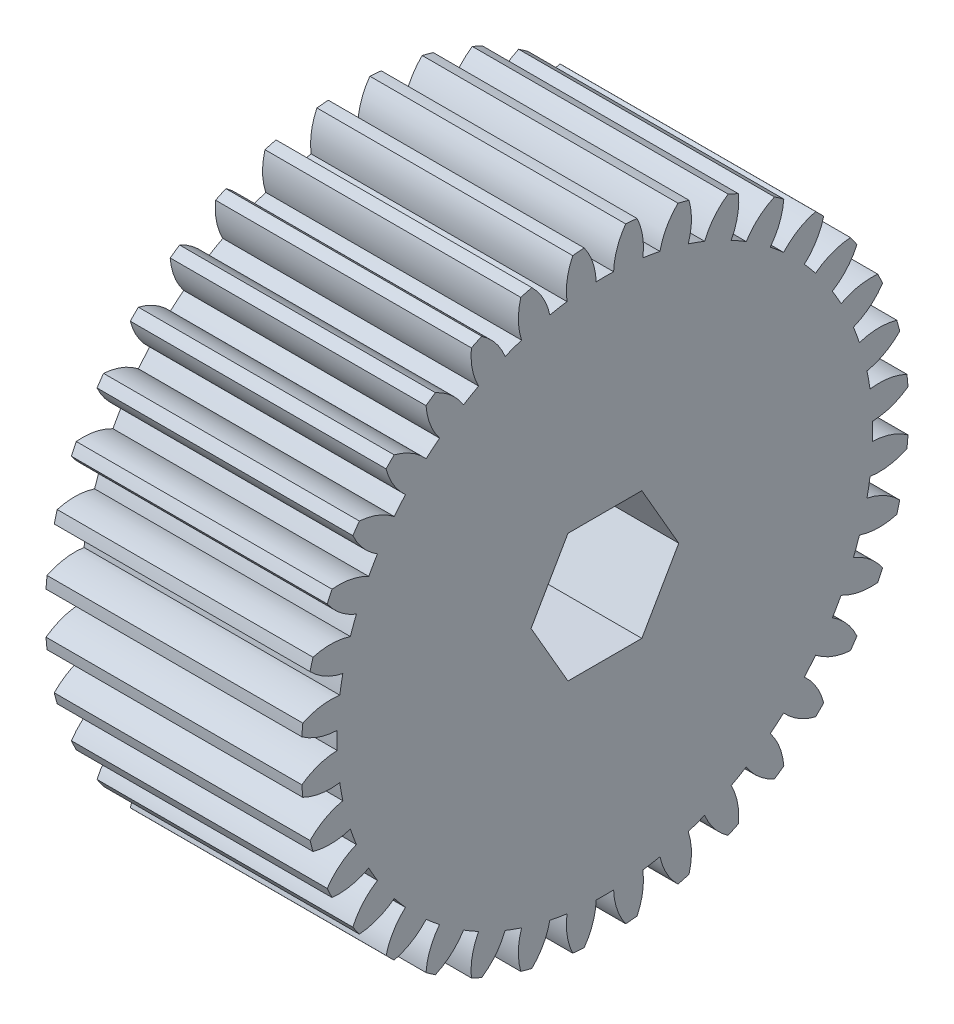
SolidWorks part; units mm, degrees
material "ABS"
ref_plane "Front Plane" through (0, 0, 0) normal (0, 0, 1) x (1, 0, 0)
ref_plane "Top Plane" through (0, 0, 0) normal (0, 1, 0) x (1, 0, 0)
ref_plane "Right Plane" through (0, 0, 0) normal (1, 0, 0) x (0, 0, -1)
sketch "Sketch1" plane through (0, 0, 0) normal (1, 0, 0) x (0, 0, -1)
  circle A0 centre (0, 0) radius 28.575
  circle A1 centre (0, 0) radius 30.1625
  circle A2 centre (0, 0) radius 26.5906
  dimension "D1" = 57.15
  dimension "D2" = 1.5875
  dimension "D3" = 3.5719
extrude "Boss-Extrude1" add sketch "Sketch1" along normal blind 25.4 contours A2 | A0 A2 | A1 A0 region at (0, 0, 27.7668) region at (0, 0, 29.3094) region at (0, 0, 0)
sketch "Sketch2" plane through (25.4, 0, 0) normal (1, 0, 0) x (0, 0, -1)
  line L0 (0, 0) -> (0, 30.1625) construction
  line L1 (0, 25.1233) -> (-1.2464, 28.5478) construction
  line L2 (-1.2464, 28.5478) -> (1.2464, 28.5478) construction
  line L3 (1.2464, 28.5478) -> (3.7298, 28.3305) construction
  line L4 (2.4881, 28.4392) -> (0, 0) construction
  line L5 (-0.8656, 26.5765) -> (0, 0) construction
  circle A0 centre (0, 0) radius 30.1625 construction
  arc A1 (-0.8656, 26.5765) -> (-2.6937, 30.8388) centre (-7.2322, 26.3692) ccw
  circle A2 centre (0, 0) radius 26.5906
  arc A3 (0.8656, 26.5765) -> (-0.8656, 26.5765) centre (0, 0) ccw
  circle A4 centre (0, 0) radius 30.1625
  circle A5 centre (0, 0) radius 30.1625 construction
  circle A6 centre (0, 0) radius 28.575
  circle A7 centre (0, 0) radius 28.575 construction
  arc A8 (2.6937, 30.8388) -> (-2.6937, 30.8388) centre (0, 0) ccw
  arc A9 (0.8656, 26.5765) -> (2.6937, 30.8388) centre (7.2322, 26.3692) cw
  point P22 (0, 11.9182)
  point P26 (-1.1112, 15.9084)
  dimension "D4" = 0.7937
  dimension "D5" = 5
  dimension "D6" = 20
extrude "Cut-Extrude1" cut sketch "Sketch2" against normal through all
pattern_circular "CirPattern1" count 36 over 360 about axis through (25.4, 0, 0) along (-1, 0, 0) of "Cut-Extrude1" reverse direction yes
sketch "Sketch3" plane through (25.4, 0, 0) normal (1, 0, 0) x (0, 0, -1)
  line L1 (3.6662, 6.35) -> (-3.6662, 6.35)
  line L2 (-3.6662, 6.35) -> (-7.3323, 0)
  line L3 (-7.3323, 0) -> (-3.6662, -6.35)
  line L4 (-3.6662, -6.35) -> (3.6662, -6.35)
  line L5 (3.6662, -6.35) -> (7.3323, 0)
  line L6 (7.3323, 0) -> (3.6662, 6.35)
  circle A0 centre (0, 0) radius 6.35 construction
  dimension "D1" = 12.7
extrude "Cut-Extrude2" cut sketch "Sketch3" against normal through all
sketch "Sketch4" plane through (25.4, 0, 0) normal (1, 0, 0) x (0, 0, -1)
  circle A0 centre (0, 0) radius 28.575
  point P2 (0, 0)
  dimension "D1" = 57.15
equation "\"Module\"= 1 / 16in"
equation "\"Number of Teeth\"= 36"
equation "\"D1@Sketch1\"=\"Module\" * \"Number of Teeth\""
equation "\"D2@Sketch1\"=\"Module\""
equation "\"D3@Sketch1\"=2.25 * \"Module\""
equation "\"D5@Sketch2\"=180 / \"Number of Teeth\""
equation "\"D1@CirPattern1\"=\"Number of Teeth\""
equation "\"D1@Sketch4\"=\"Module\" * \"Number of Teeth\""
